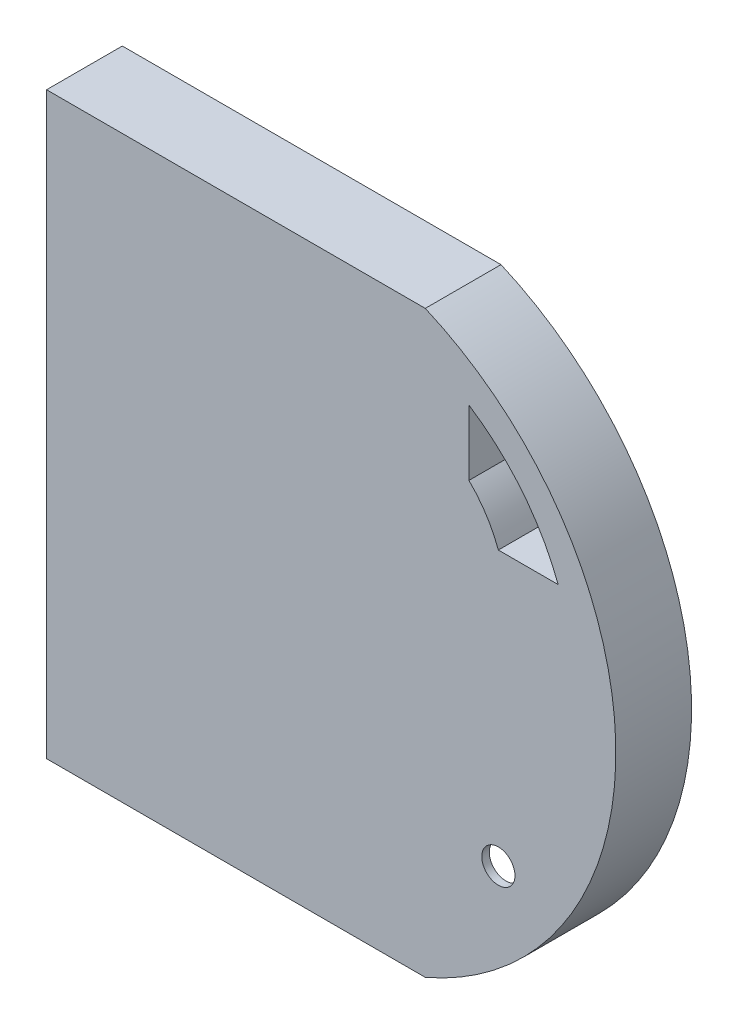
SolidWorks part; units mm, degrees
ref_plane "Front Plane" through (0, 0, 0) normal (0, 0, 1) x (1, 0, 0)
ref_plane "Top Plane" through (0, 0, 0) normal (0, 1, 0) x (1, 0, 0)
ref_plane "Right Plane" through (0, 0, 0) normal (1, 0, 0) x (0, 0, -1)
sketch "Sketch1" plane through (0, 0, 0) normal (0, 0, 1) x (1, 0, 0)
  line L1 (-74.2297, 45.7275) -> (-49.2297, 45.7275)
  line L2 (-74.2297, 45.7275) -> (-74.2297, 5.7275)
  line L3 (-74.2297, 5.7275) -> (-49.2297, 5.7275)
  line L4 (-49.2297, 45.7275) -> (-49.2297, 5.7275)
  dimension "D1" = 40
  dimension "D2" = 25
extrude "Boss-Extrude1" add sketch "Sketch1" along normal blind 0.5 and the other way blind 0.0001
sketch "Sketch2" plane through (0, 0, 0) normal (0, 0, 1) x (1, 0, 0)
  line L0 (-77.8888, 47.5275) -> (-77.8888, 3.9275)
  line L5 (-61.7297, 45.7275) -> (-61.7297, 25.7275)
  line L6 (-49.2297, 45.7275) -> (-74.2297, 45.7275) construction
  line L8 (-77.8888, 47.5275) -> (-49.3888, 47.5275)
  line L10 (-77.8888, 3.9275) -> (-49.3888, 3.9275)
  circle A1 centre (-42.3892, 25.7624) radius 48.5612
  arc A3 (-49.3888, 47.5275) -> (-49.3888, 3.9275) centre (-58.7867, 25.7275) cw
  dimension "D6" = 43.6
  dimension "D8" = 28.5
  dimension "D9" = 28.5
extrude "Boss-Extrude5" add sketch "Sketch2" along normal blind 5.6 and the other way blind 0.1 contours L8 L0 region at (-58.2685, 25.7275, 0)
sketch "Sketch8" plane through (0, 0, 0) normal (0, 0, 1) x (1, 0, 0)
  line L0 (-76.8888, 46.5275) -> (-76.8888, 4.9275)
  line L1 (-76.8888, 4.9275) -> (-49.3888, 4.9275)
  line L2 (-76.8888, 46.5275) -> (-49.3888, 46.5275)
  line L3 (-77.8888, 47.5275) -> (-77.8888, 3.9275) construction
  arc A0 (-49.3888, 4.9275) -> (-49.3888, 46.5275) centre (-58.9321, 25.7275) ccw
  arc A2 (-49.3888, 3.9275) -> (-49.3888, 47.5275) centre (-58.7867, 25.7275) ccw construction
  point P8 (-36.0473, 25.7275)
  point P12 (-35.0473, 25.7275)
  dimension "D1" = 1
  dimension "D2" = 1
  dimension "D3" = 1
  dimension "D4" = 1
extrude "Cut-Extrude2" cut sketch "Sketch8" against normal blind 1 and the other way blind 5.0339 contours A0 L2 L0 L1
sketch "Sketch9" plane through (0, 0, 0) normal (0, 0, 1) x (1, 0, 0)
  line L0 (-37.7093, 30.2625) -> (-37.7093, 29.3916)
  line L1 (-37.7093, 22.0742) -> (-37.7093, 21.228)
  line L2 (-46.6022, 30.9745) -> (-46.6022, 30.0766)
  line L3 (-46.6022, 21.3784) -> (-46.6022, 20.6468)
  arc A3 (-37.7093, 30.2625) -> (-46.6022, 30.9745) centre (-42.5385, 25.8379) ccw
  arc A4 (-37.7093, 21.228) -> (-46.6022, 20.6468) centre (-42.4688, 25.7275) cw
  arc A5 (-37.7093, 29.3916) -> (-46.6022, 30.0766) centre (-42.4641, 25.732) ccw
  arc A6 (-37.7093, 22.0742) -> (-46.6022, 21.3784) centre (-42.4688, 25.7275) cw
  point P0 (0, 0)
sketch "Sketch11" plane through (0, 0, -0.1) normal (0, 0, -1) x (-1, 0, 0)
  line L2 (49.3888, 4.4275) -> (77.3888, 4.4275)
  line L4 (77.3888, 47.0275) -> (49.3888, 47.0275)
  line L7 (77.3888, 47.0275) -> (77.3888, 4.4275)
  line L8 (76.8888, 46.5275) -> (76.8888, 4.9275)
  line L9 (76.8888, 4.9275) -> (49.3888, 4.9275)
  line L12 (76.8888, 46.5275) -> (49.3888, 46.5275)
  arc A0 (49.3888, 47.0275) -> (49.3888, 4.4275) centre (58.8568, 25.7275) ccw
  arc A1 (49.3888, 47.5275) -> (49.3888, 3.9275) centre (58.7867, 25.7275) ccw construction
  arc A4 (49.3888, 46.5275) -> (49.3888, 4.9275) centre (58.9321, 25.7275) ccw
  point P0 (0, 0)
  point P16 (35.0473, 25.7275)
  point P17 (35.5473, 25.7275)
  point P19 (0, 0)
  point P20 (0, 0)
  point P22 (0, 0)
  point P24 (0, 0)
  point P28 (0, 0)
  point P30 (0, 0)
  point P31 (0, 0)
  point P32 (0, 0)
  point P33 (0, 0)
  point P34 (0, 0)
  point P35 (49.3888, 46.5275)
  point P36 (0, 0)
  point P37 (0, 0)
  point P38 (0, 0)
  point P39 (0, 0)
  point P40 (0, 0)
  point P41 (0, 0)
  dimension "D1" = 0.5
  dimension "D2" = 0.5
  dimension "D4" = 0.5
extrude "Cut-Extrude3" cut sketch "Sketch11" against normal blind 0.5 contours L4 A0 L2 L7
extrude "Boss-Extrude7" add sketch "Sketch9" along normal blind 5 and the other way blind 1 separate body contours A4 L3 A6 L1 | A3 L2 A5 L0
sketch "Sketch17" plane through (-77.8888, 0, 0) normal (-1, 0, 0) x (0, 0, 1)
  line L3 (-3.1, 25.7275) -> (-3.1, 28.7275)
  line L4 (-3.1, 25.7275) -> (-3.1, 22.7275)
  line L5 (-3.1, 22.7275) -> (2.9, 25.7275)
  line L6 (-3.1, 28.7275) -> (2.9, 25.7275)
extrude "Cut-Extrude4" cut sketch "Sketch17" against normal blind 0.4
sketch "Sketch18" plane through (0, 0, 5.0339) normal (0, 0, -1) x (-1, 0, 0)
  line L3 (39.3888, 34.5275) -> (43.8888, 34.5275)
  line L6 (46.1022, 37.9588) -> (46.1022, 42.8646)
  arc A4 (43.8888, 34.5275) -> (46.1022, 37.9588) centre (52.5399, 31.3763) cw
  arc A5 (39.3888, 34.5275) -> (46.1022, 42.8646) centre (55.4535, 28.4628) cw
sketch "Sketch19" plane through (0, 0, 0.4) normal (0, 0, -1) x (-1, 0, 0)
sketch "Sketch29" plane through (0, 0, 5.0339) normal (0, 0, -1) x (-1, 0, 0)
  line L0 (49.3888, 4.9275) -> (49.3888, 13.9275)
  line L1 (49.3888, 13.9275) -> (43.8888, 13.9275)
  circle A0 centre (43.8888, 13.9275) radius 1.25
  circle A1 centre (43.8888, 13.9275) radius 2.5
  dimension "D1" = 2.5
  dimension "D2" = 5
sketch "Sketch33" plane through (-77.8888, 0, 0) normal (-1, 0, 0) x (0, 0, 1)
  line L0 (5.0339, 17.0721) -> (5.6, 17.0721)
  line L1 (5.0339, 46.5275) -> (5.0339, 4.9275) construction
  line L2 (5.6, 3.9275) -> (5.6, 47.5275) construction
extrude "Cut-Extrude7" cut sketch "Sketch29" against normal blind 6.2 and the other way blind 5 contours A0
sketch "Sketch35" plane through (0, 0, 5.0339) normal (0, 0, -1) x (-1, 0, 0)
extrude "Cut-Extrude10" cut sketch "Sketch18" against normal blind 3.2 and the other way blind 12
sketch "Sketch38" plane through (0, 0, 5.0339) normal (0, 0, -1) x (-1, 0, 0)
  line L0 (38.8722, 34.0447) -> (44.4053, 34.0447)
  line L4 (46.6022, 42.8646) -> (46.6022, 43.6146)
  line L8 (46.6022, 37.9588) -> (46.6022, 37.7088)
  line L11 (43.8888, 34.0447) -> (44.4053, 34.0447)
  line L15 (39.3888, 34.0447) -> (38.8722, 34.0447)
  line L17 (46.6022, 43.6146) -> (46.6022, 37.7088)
  arc A0 (38.8722, 34.0447) -> (46.6022, 43.6146) centre (55.0658, 28.8712) cw
  arc A1 (44.4053, 34.0447) -> (46.6022, 37.7088) centre (52.5599, 31.6461) cw
  arc M14 (46.1022, 37.9588) -> (43.8888, 34.5275) centre (52.5399, 31.3763) ccw
  line M15 (43.8888, 34.5275) -> (39.3888, 34.5275)
  arc M16 (39.3888, 34.5275) -> (46.1022, 42.8646) centre (55.4535, 28.4628) cw
  line M17 (46.1022, 42.8646) -> (46.1022, 37.9588)
extrude "Boss-Extrude15" add sketch "Sketch38" along normal blind 5.134 and the other way blind 0.5 contours L0 A1 L8 L17 L4 A0 M17 M14 M15 M16 region at (-41.9369, 39.4761, 5.0339)
sketch "Sketch39" plane through (0, 0, -0.1001) normal (0, 0, -1) x (-1, 0, 0)
  arc A0 (43.8888, 34.5275) -> (46.1022, 37.9588) centre (52.5399, 31.3763) cw
  point P3 (45.1605, 37.769)
sketch "Sketch40" plane through (0, 0, 5.0339) normal (0, 0, -1) x (-1, 0, 0)
  line L1 (44.4053, 34.0447) -> (43.8888, 34.0447)
  line L5 (38.8722, 34.0447) -> (39.3888, 34.0447)
  point P15 (46.7031, 38.1845)
sketch "Sketch42" plane through (-77.8888, 0, 0) normal (-1, 0, 0) x (0, 0, 1)
  line L0 (-0.1, 47.5275) -> (-0.1, 36.8775)
  line L1 (-0.1, 47.5275) -> (-0.1, 27.2275) construction
  line L2 (2.3, 11.3275) -> (2.3, 12.3275)
  line L4 (0.65, 39.1275) -> (0.65, 47.5275)
  line L5 (1.9, 36.8775) -> (1.9, 39.1275)
  line L6 (1.9, 39.1275) -> (0.65, 39.1275)
  line L7 (0.65, 39.1275) -> (0.65, 34.6275)
  line L8 (0.65, 34.6275) -> (1.9, 34.6275)
  line L9 (1.9, 34.6275) -> (1.9, 36.8775)
  line L10 (-0.1, 47.5275) -> (5.6, 47.5275) construction
  line L11 (2.3, 12.3275) -> (0.4, 12.3275)
  line L12 (2.3, 17.8275) -> (2.3, 16.8275)
  line L13 (1.9, 12.3275) -> (0.65, 12.3275)
  line L14 (1.9, 12.3275) -> (1.9, 16.8275)
  line L16 (0.65, 12.3275) -> (0.65, 16.8275)
  line L17 (1.9, 17.8275) -> (0.65, 17.8275)
  line L18 (1.9, 11.3275) -> (0.65, 11.3275)
  line L19 (0.4, 17.8275) -> (2.3, 17.8275)
  line L20 (0.4, 47.0275) -> (0.4, 4.4275) construction
  line L21 (0.4, 11.3275) -> (2.3, 11.3275)
  line L22 (2.3, 16.8275) -> (0.4, 16.8275)
  line L23 (0.4, 17.8275) -> (0.4, 16.8275)
  line L24 (0.4, 12.3275) -> (0.4, 11.3275)
extrude "Boss-Extrude21" add sketch "Sketch42" against normal blind 2.001 contours L19 L23 L22 L12 L17 | L11 L24 L21 L18 L2 region at (-77.8888, 11.8275, 1.35) region at (-77.8888, 17.3275, 1.35)
sketch "Sketch49" plane through (0, 0, 0.4) normal (0, 0, -1) x (-1, 0, 0)
  line L0 (75.8878, 17.7611) -> (75.8878, 17.8275)
  line L1 (75.8878, 17.8275) -> (75.8878, 16.8275) construction
  line L2 (75.8878, 17.8275) -> (74.8878, 17.8275)
  line L3 (74.8878, 17.8275) -> (74.8878, 11.6949)
  line L5 (75.8878, 11.3275) -> (74.8878, 11.3275)
  line L6 (74.8878, 11.3275) -> (74.8878, 11.6949)
  line L7 (75.8878, 11.3275) -> (75.8878, 17.8275)
extrude "Boss-Extrude22" add sketch "Sketch49" against normal blind 1.9 contours L2 L3 L6 L5 L7
